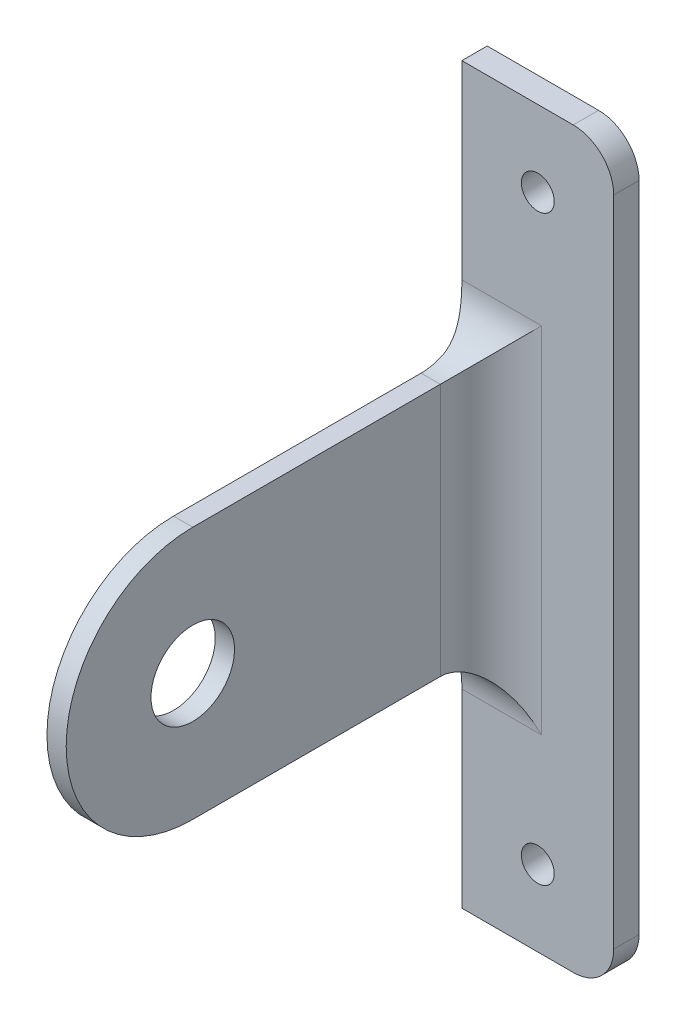
SolidWorks part; units mm, degrees
ref_plane "Front Plane" through (0, 0, 0) normal (0, 0, 1) x (1, 0, 0)
ref_plane "Top Plane" through (0, 0, 0) normal (0, 1, 0) x (1, 0, 0)
ref_plane "Right Plane" through (0, 0, 0) normal (1, 0, 0) x (0, 0, -1)
sketch "Sketch1" plane through (0, 0, 0) normal (1, 0, 0) x (0, 0, -1)
  line L1 (0, 12.5) -> (34.45, 12.5)
  line L2 (0, 4.125) -> (0, -12.5)
  line L3 (0, -12.5) -> (34.45, -12.5)
  line L4 (34.45, 12.5) -> (34.45, -12.5)
  circle A0 centre (0, 0) radius 4.125
  circle A1 centre (0, 0) radius 12.5 construction
  arc A2 (0, 12.5) -> (0, -12.5) centre (0, 0) ccw
  dimension "D1" = 8.25
  dimension "D2" = 25
  dimension "D3" = 34.45
extrude "Boss-Extrude1" add sketch "Sketch1" along normal blind 1.9 contours L1 A2 A0 L3 L4 region at (0, 0, -12.849)
sketch "Sketch2" [suppressed] plane through (0, 0, 0) normal (-1, 0, 0) x (0, 0, 1)
  circle A0 centre (0, 0) radius 1.5
  circle A1 centre (0, 0) radius 4.5
  dimension "D1" = 9
  dimension "D2" = 3
sketch "Sketch4" [suppressed] plane through (2.5, 0, 0) normal (1, 0, 0) x (0, 0, -1)
  circle A0 centre (0, 0) radius 2.5
sketch "Sketch5" [suppressed] plane through (2.5, 0, 0) normal (1, 0, 0) x (0, 0, -1)
  circle A0 centre (0, 0) radius 4.5
  circle A1 centre (0, 0) radius 2.5
  dimension "D1" = 9
  dimension "D2" = 5
sketch "Sketch6" plane through (0, 0, -34.45) normal (0, 0, -1) x (-1, 0, 0)
  line L1 (-8.8125, 36.25) -> (53.3216, 36.25)
  line L3 (6.25, -36.25) -> (53.3216, -36.25)
  line L4 (53.3216, 36.25) -> (53.3216, -36.25)
  line L6 (53.3216, -36.25) -> (-19.1784, 36.25) construction
  line L7 (6.25, -36.25) -> (-19.1784, -36.25)
  line L9 (-8.8125, 36.25) -> (-19.1784, 36.25)
  line L10 (-19.1784, -36.25) -> (-19.1784, 36.25)
  line L11 (53.3216, 36.25) -> (-19.1784, -36.25) construction
  point P4 (17.0716, 0)
  dimension "D1" = 72.5
  dimension "D2" = 72.5
extrude "Boss-Extrude4" add sketch "Sketch6" against normal blind 2.5
ref_plane "Plane1" through (-17.0716, 0, 0) normal (1, 0, 0) x (0, 0, -1)
ref_plane "Plane2" through (9.4784, 0, 0) normal (1, 0, 0) x (0, 0, -1)
sketch "Sketch7" plane through (0, 0, -31.95) normal (0, 0, 1) x (1, 0, 0)
  line L7 (1.7881, -3.3824) -> (-5.2119, -3.3824)
  line L12 (1.7881, -3.3824) -> (1.7881, -19.8824)
  line L18 (1.7881, -19.8824) -> (-5.2119, -19.8824)
  line L19 (-5.2119, -3.3824) -> (-5.2119, -19.8824)
  line L20 (1.7881, -3.3824) -> (-5.2119, -19.8824) construction
  line L21 (1.7881, -19.8824) -> (-5.2119, -3.3824) construction
  line L22 (-24.5, -4) -> (-8.5, -4)
  line L23 (-24.5, -4) -> (-24.5, 4)
  line L24 (-24.5, 4) -> (-8.5, 4)
  line L25 (-8.5, -4) -> (-8.5, 4)
  line L26 (-24.5, -4) -> (-8.5, 4) construction
  line L27 (-24.5, 4) -> (-8.5, -4) construction
  point P0 (-16.5, 0)
  point P2 (-1.7119, -11.6324)
  dimension "D1" = 16
  dimension "D2" = 16.5
  dimension "D3" = 7
  dimension "D4" = 8
extrude "Cut-Extrude2" cut sketch "Sketch7" against normal up to next
sketch "Sketch8" plane through (0, 0, 0) normal (0, 1, 0) x (1, 0, 0)
  line L10 (1.9, 4.125) -> (0, 4.125)
  line L15 (1.9, 4.125) -> (1.9, 31.95)
  line L16 (1.9, 31.95) -> (0, 31.95)
  line L21 (0, 4.125) -> (0, 31.95)
sketch "Sketch9" plane through (0, -12.5, 0) normal (0, -1, 0) x (1, 0, 0)
  line L0 (1.9, 0) -> (1.9, -31.95) construction
  line L1 (0, -31.95) -> (1.9, -31.95)
  line L2 (0, -31.95) -> (0, -9.5612)
  line L3 (0, -9.5612) -> (1.9, -9.5612)
  line L4 (1.9, -31.95) -> (1.9, -9.5612)
extrude "Cut-Extrude3" cut sketch "Sketch9" against normal up to next
extrude "Boss-Extrude5" add sketch "Sketch8" along normal mid plane 25
fillet "Fillet1" [suppressed] radius 4
fillet "Fillet2" radius 1 8 edges at (-5.2119, -3.3824, -33.2) (-5.2119, -19.8824, -33.2) (1.7881, -3.3824, -33.2) (-8.5, 4, -33.2) (1.7881, -19.8824, -33.2) (-8.5, -4, -33.2) (-24.5, 4, -33.2) (-24.5, -4, -33.2)
fillet "Fillet3" radius 4 4 edges at (19.1784, -36.25, -33.2) (19.1784, 36.25, -33.2) (-53.3216, 36.25, -33.2) (-53.3216, -36.25, -33.2)
sketch "Sketch10" plane through (0, 0, 0) normal (0, 1, 0) x (1, 0, 0)
  line L0 (15.1784, 31.95) -> (19.1784, 31.95) construction
  line L1 (21.7259, 31.95) -> (-56.5098, 31.95)
  line L2 (21.7259, 31.95) -> (21.7259, 38.24)
  line L3 (21.7259, 38.24) -> (-56.5098, 38.24)
  line L4 (-56.5098, 31.95) -> (-56.5098, 38.24)
extrude "Cut-Extrude4" cut sketch "Sketch10" against normal through all both and the other way through all
sketch "Sketch11" plane through (0, 0, 0) normal (0, 1, 0) x (1, 0, 0)
  line L1 (14.03, 31.95) -> (-0.97, 31.95)
  line L2 (14.03, 31.95) -> (14.03, 29.45)
  line L3 (14.03, 29.45) -> (-0.97, 29.45)
  line L4 (-0.97, 31.95) -> (-0.97, 29.45)
  line L6 (1.9, 31.95) -> (0, 31.95) construction
  line L7 (0, 31.95) -> (0, 0) construction
  point P4 (0, 0)
  point P5 (0, 0)
  point P6 (-2.9335, 31.8512)
  point P7 (0, 31.95)
  point P8 (0, 0)
  point P9 (-1.0774, 32.432)
  dimension "D1" = 2.5
  dimension "D2" = 15
  dimension "D3" = 0.97
extrude "Boss-Extrude6" add sketch "Sketch11" along normal mid plane 25
sketch "Sketch12" plane through (0, 0, -31.95) normal (0, 0, -1) x (-1, 0, 0)
  line L0 (1.045, 0) -> (-1.045, 0) construction
  line L1 (-14.03, 36.25) -> (58.47, 36.25) construction
  line L2 (-14.03, 36.25) -> (-14.03, -36.25) construction
  line L3 (-14.03, -36.25) -> (58.47, -36.25) construction
  line L4 (58.47, 36.25) -> (58.47, -36.25) construction
  line L5 (-14.03, 36.25) -> (58.47, -36.25) construction
  line L6 (58.47, 36.25) -> (-14.03, -36.25) construction
  line L7 (-14.03, 12.5) -> (-14.03, -12.5) construction
  circle A0 centre (-6.53, 28.75) radius 1.5
  circle A1 centre (-6.53, -28.75) radius 1.5
  circle A2 centre (-6.53, 28.75) radius 3
  circle A3 centre (-6.53, -28.75) radius 3
  point P4 (-14.03, 0)
  dimension "D3" = 3
  dimension "D5" = 6
  dimension "D1" = 72.5
  dimension "D2" = 72.5
  dimension "D4" = 7.5
sketch "Sketch13" plane through (0, 0, -31.95) normal (0, 0, -1) x (-1, 0, 0)
  line L0 (-14.03, 12.5) -> (0.97, 12.5) construction
  line L1 (-14.03, 12.5) -> (0.97, 12.5)
  line L2 (-14.03, 12.5) -> (-14.03, 32.25)
  line L4 (0.97, 12.5) -> (0.97, 36.25)
  line L5 (0.97, 36.25) -> (-10.03, 36.25)
  arc A1 (-10.03, 36.25) -> (-14.03, 32.25) centre (-10.03, 32.25) ccw
  point P2 (0, 0)
  point P4 (0, 0)
  point P7 (0, 0)
  point P8 (-11.7751, 32.25)
  point P10 (0, 0)
  point P11 (-0.4135, 36.25)
  point P12 (0, 0)
  point P13 (-2.65, 12.5)
  point P16 (-2.65, 28.75)
  point P17 (0, 12.5)
  point P18 (0, 0)
  point P19 (-9.7829, 32.0417)
  point P21 (0, 0)
  point P22 (0, 0)
  point P23 (0, 0)
  point P24 (0, 0)
  point P25 (0, 0)
  point P26 (0, 35.948)
  point P27 (0.97, 12.5)
  point P29 (0, 0)
  point P30 (0, 0)
  point P31 (0, 0)
  dimension "D2" = 4
  dimension "D1" = 4
  dimension "D3" = 15
  dimension "D4" = 36.25
  dimension "D5" = 4
extrude "Boss-Extrude7" add sketch "Sketch13" against normal blind 2.5
mirror "Mirror1" about plane through (0, 0, 0) normal (0, 1, 0) of "Boss-Extrude6", "Boss-Extrude7"
sketch "Sketch14" plane through (0, 0, -31.95) normal (0, 0, -1) x (-1, 0, 0)
  line L1 (0.97, -36.25) -> (0.97, 36.25) construction
  line L2 (0.97, 36.25) -> (-10.03, 36.25) construction
  circle A0 centre (-6.53, 28.75) radius 1.625
  dimension "D3" = 3.25
  dimension "D1" = 7.5
  dimension "D2" = 7.5
extrude "Cut-Extrude5" cut sketch "Sketch14" against normal blind 2.5
sketch "Sketch15" [suppressed] plane through (0, 0, -31.95) normal (0, 0, -1) x (-1, 0, 0)
  circle A0 centre (-6.4288, 28.75) radius 2.5
  circle A1 centre (-6.4288, 28.75) radius 4
  dimension "D1" = 8
  dimension "D2" = 5
extrude "Boss-Extrude8" [suppressed] add sketch "Sketch15" against normal blind 6
mirror "Mirror2" about plane through (0, 0, 0) normal (0, 1, 0) of "Cut-Extrude5", "Boss-Extrude8"
fillet "Fillet4" radius 5 4 edges at (0.95, -12.5, -29.45) (0, 0, -29.45) (0.95, 12.5, -29.45) (1.9, 0, -29.45)
